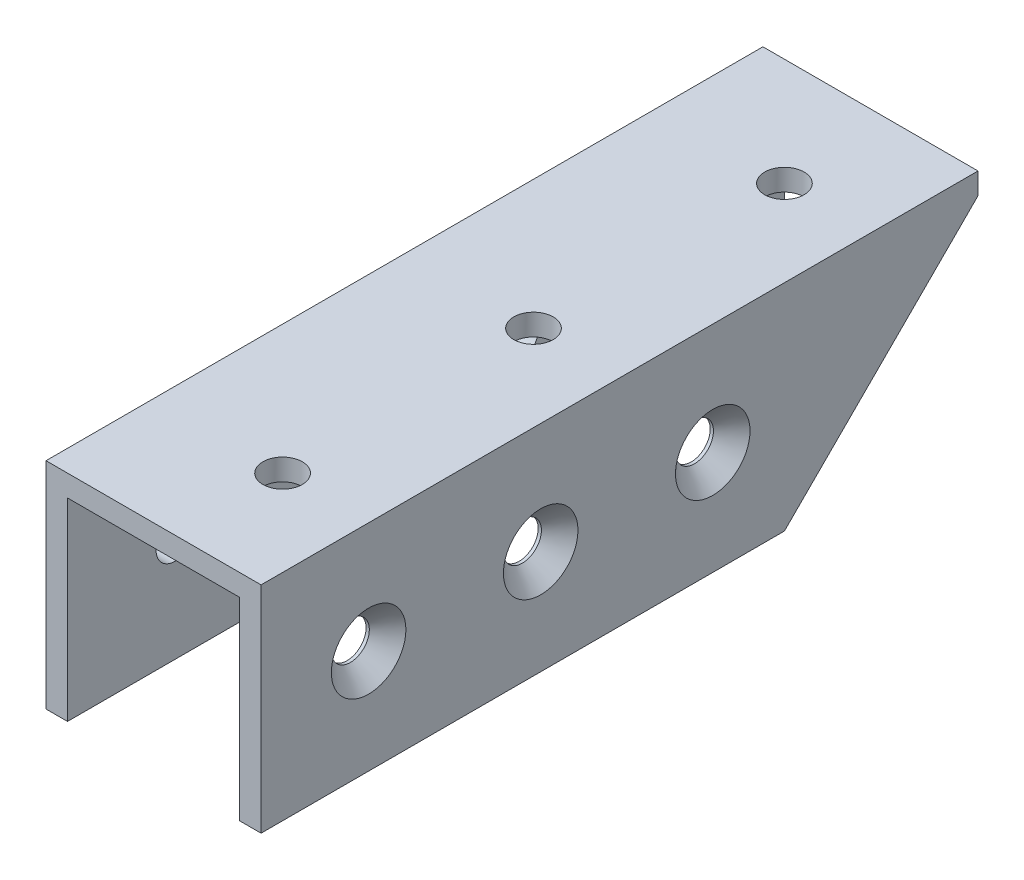
SolidWorks part; units mm, degrees
material "1060 Alloy"
ref_plane "Płaszczyzna przednia" through (0, 0, 0) normal (0, 0, 1) x (1, 0, 0)
ref_plane "Płaszczyzna górna" through (0, 0, 0) normal (0, 1, 0) x (1, 0, 0)
ref_plane "Płaszczyzna prawa" through (0, 0, 0) normal (1, 0, 0) x (0, 0, -1)
sketch "Szkic1" plane through (0, 0, 0) normal (0, 0, 1) x (1, 0, 0)
  line L0 (0, 0) -> (0, 30)
  line L1 (0, 30) -> (30, 30)
  line L2 (30, 30) -> (30, 0)
  line L3 (30, 0) -> (27, 0)
  line L4 (27, 0) -> (27, 27)
  line L5 (27, 27) -> (3, 27)
  line L6 (3, 27) -> (3, 0)
  line L7 (3, 0) -> (0, 0)
  dimension "D1" = 3
  dimension "D2" = 3
  dimension "D3" = 3
  dimension "D4" = 30
  dimension "D5" = 30
extrude "Dodanie-wyciągnięcie1" add sketch "Szkic1" along normal blind 100
hole_wizard "M5 Clearance Hole1" positions "Sketch1" profile "Sketch2" hole size "M5" standard "ISO" end condition through all
sketch "Sketch1" plane through (0, 30, 0) normal (0, 1, 0) x (1, 0, 0)
  line L0 (30, -100) -> (0, -100) construction
  line L1 (30, -100) -> (30, 0) construction
  point P0 (18, -50)
  point P2 (18, -15)
  point P4 (18, -85)
  dimension "D1" = 35
  dimension "D2" = 35
  dimension "D3" = 15
  dimension "D4" = 12
sketch "Sketch2" plane through (18, 30, 50) normal (1, 0, 0) x (0, 0, 1)
  line L0 (0, 0) -> (0, 30)
  line L1 (0, 30) -> (2.75, 30)
  line L2 (2.75, 30) -> (2.75, 0)
  line L5 (2.75, 0) -> (0, 0)
  line L11 (0, -6.35) -> (0, 107.95) construction
  dimension "Thru Hole Dia." = 5.5
  dimension "Thru Hole Depth" = 30
hole_wizard "CSK for M5 Countersunk Flat Head Screw1" positions "Sketch3" profile "Sketch4" countersink size "M5" standard "DIN" end condition through all
sketch "Sketch3" plane through (30, 0, 0) normal (1, 0, 0) x (0, 0, -1)
  line L3 (-100, 27) -> (0, 27) construction
  line L4 (-100, 0) -> (-100, 30) construction
  point P0 (-37, 14.5)
  point P2 (-85, 14.5)
  point P4 (-61, 14.5)
  dimension "D1" = 24
  dimension "D2" = 24
  dimension "D3" = 15
  dimension "D4" = 12.5
sketch "Sketch4" plane through (30, 14.5, 37) normal (0, 1, 0) x (0, 0, -1)
  line L0 (0, 0) -> (0, 30)
  line L1 (0, 30) -> (2.65, 30)
  line L2 (2.65, 30) -> (2.65, 2.55)
  line L3 (2.65, 2.55) -> (5.2, 0)
  line L5 (5.2, 0) -> (0, 0)
  line L6 (-2.65, 2.55) -> (-5.2, 0) construction
  line L11 (0, -6.35) -> (0, 107.95) construction
  dimension "Thru Hole Dia." = 5.3
  dimension "Thru Hole Depth" = 30
  dimension "Near C'Sink Dia." = 10.4
  dimension "Near C'Sink Angle" = 90
chamfer "Chamfer1" distance 27 angle 45 1 edges at (28.5, 0, 0)
